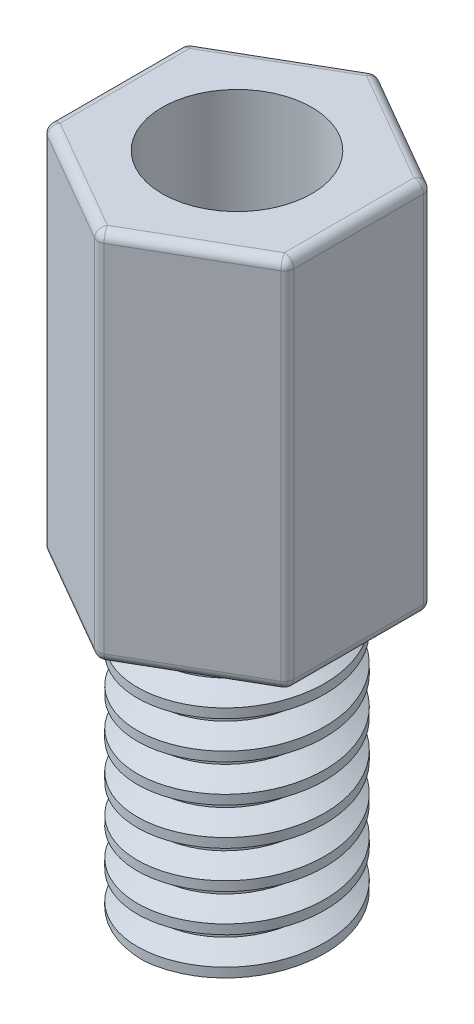
SolidWorks part; units mm, degrees
ref_plane "前视基准面" through (0, 0, 0) normal (0, 0, 1) x (1, 0, 0)
ref_plane "上视基准面" through (0, 0, 0) normal (0, 1, 0) x (1, 0, 0)
ref_plane "右视基准面" through (0, 0, 0) normal (1, 0, 0) x (0, 0, -1)
sketch "草图1" plane through (0, 0, 0) normal (0, 1, 0) x (1, 0, 0)
  line L0 (-1.299, 0.75) -> (1.299, -0.75) construction
  line L1 (1.299, 0.75) -> (-1.299, -0.75) construction
  line L2 (0, 1.5) -> (0, -1.5) construction
  line L3 (-1.299, 0.75) -> (0, 1.5)
  line L4 (0, 1.5) -> (1.299, 0.75)
  line L5 (1.299, 0.75) -> (1.299, -0.75)
  line L6 (1.299, -0.75) -> (0, -1.5)
  line L7 (0, -1.5) -> (-1.299, -0.75)
  line L8 (-1.299, -0.75) -> (-1.299, 0.75)
  circle A0 centre (0, 0) radius 1.5 construction
  point P12 (0, 0)
extrude "凸台-拉伸1" add sketch "草图1" along normal blind 7
sketch "草图2" plane through (0, 7, 0) normal (0, 1, 0) x (1, 0, 0)
  circle A0 centre (0, 0) radius 1
hole_wizard "M2 螺纹孔1" positions "草图3" profile "草图4" tap size "M2" standard "ISO"
sketch "草图3" plane through (0, 7, 0) normal (0, 1, 0) x (1, 0, 0)
  point P0 (0, 0)
sketch "草图4" plane through (0, 7, 0) normal (1, 0, 0) x (0, 0, 1)
  line L0 (0, 0) -> (0, 3.9807)
  line L1 (0, 3.9807) -> (0.8, 3.5)
  line L2 (0.8, 3.5) -> (0.8, 0)
  line L5 (0.8, 0) -> (0, 0)
  line L10 (0, 3.9807) -> (-0.8, 3.5) construction
  line L11 (0, -6.35) -> (0, 107.95) construction
  dimension "螺纹孔钻头直径" = 1.6
  dimension "螺纹孔钻头深度" = 3.5
  dimension "导头角度" = 118
cosmetic thread "孔螺蚊线1" parameters "D1"=3.5, "D2"=2
sketch "草图6" plane through (0, 0, 0) normal (0, -1, 0) x (1, 0, 0)
  circle A0 centre (0, 0) radius 1
  circle A1 centre (0, 0) radius 1.9435
extrude "切除-拉伸1" cut sketch "草图6" against normal blind 3
thread "螺纹线1" pitch 0.4 method cut profile "螺纹线轮廓2" start angle 0, offset 1, length 3.8, pitch 0.4, diameter 2
ref_plane "基准面2" through (1, -1, 0) normal (0, 0, 1) x (1, 0, 0)
sketch "螺纹线轮廓2" plane through (1, -1, 0) normal (0, 0, 1) x (1, 0, 0)
  line L0 (0, 0) -> (0, 0.4) construction
  line L1 (0, 0.3) -> (-0.2165, 0.175)
  line L2 (-0.2165, 0.175) -> (-0.2165, 0.125)
  line L3 (-0.2165, 0.125) -> (0, 0)
  line L4 (-0.2165, 0.15) -> (0, 0.15) construction
  line L11 (0, 0.3) -> (0, 0)
  point P6 (0, 0)
  dimension "Pitch" = 0.4
  dimension "Profile_Angle" = 60
  dimension "Profile_Land" = 0.05
  dimension "Profile_Height" = 0.2165
fillet "圆角1" radius 0.1 18 edges at (1.299, 3, 0) (0.6495, 3, -1.125) (0.6495, 3, 1.125) (-1.299, 3, 0) (-0.6495, 3, 1.125) (-0.6495, 7, -1.125) (0.6495, 7, -1.125) (1.299, 7, 0) (0.6495, 7, 1.125) (-0.6495, 7, 1.125) (-1.299, 7, 0) (0, 5, 1.5) (-1.299, 5, 0.75) (-1.299, 5, -0.75) (0, 5, -1.5) (1.299, 5, 0.75) (1.299, 5, -0.75) (-0.6495, 3, -1.125)
